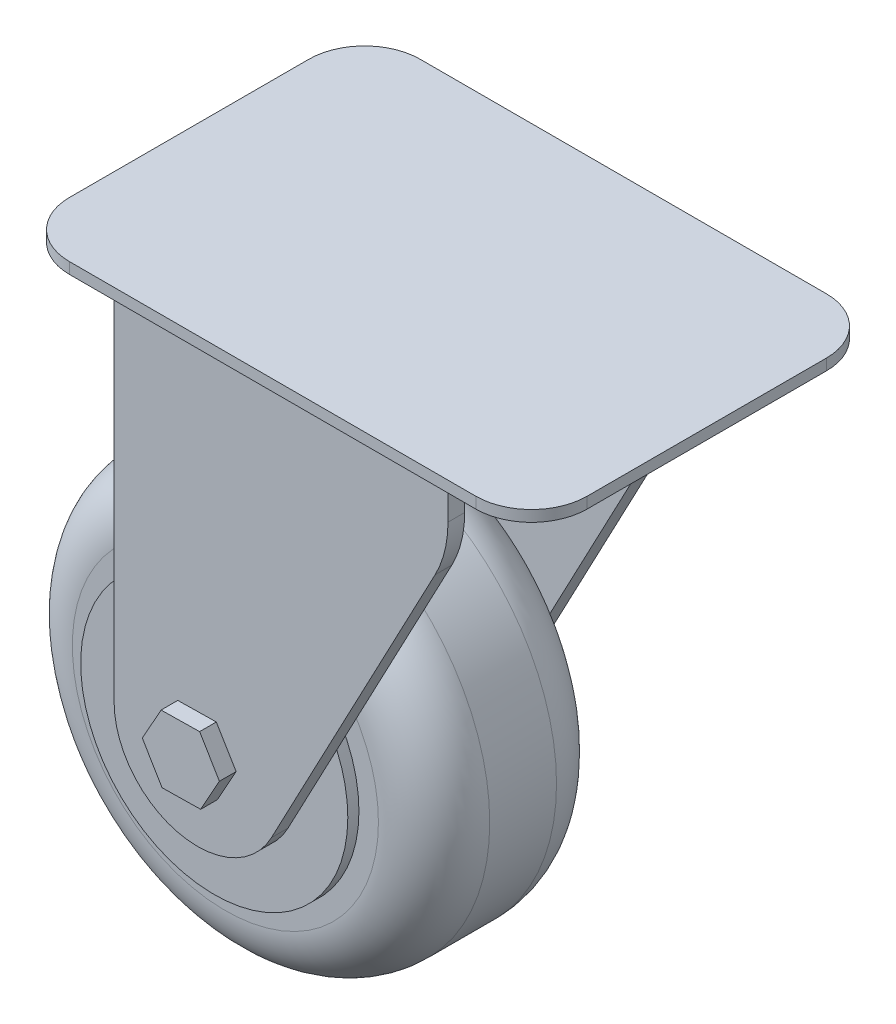
SolidWorks part; units mm, degrees
ref_plane "정면" through (0, 0, 0) normal (0, 0, 1) x (1, 0, 0)
ref_plane "윗면" through (0, 0, 0) normal (0, 1, 0) x (1, 0, 0)
ref_plane "우측면" through (0, 0, 0) normal (1, 0, 0) x (0, 0, -1)
sketch "스케치1" plane through (0, 0, 0) normal (0, 0, 1) x (1, 0, 0)
  line L0 (0, 0) -> (48.102, 0) construction
  line L1 (3.3687, 6.0541) -> (-3.5586, 5.9444)
  line L2 (-3.5586, 5.9444) -> (-6.9273, -0.1096)
  line L3 (-6.9273, -0.1096) -> (-3.3687, -6.0541)
  line L4 (-3.3687, -6.0541) -> (3.5586, -5.9444)
  line L5 (3.5586, -5.9444) -> (6.9273, 0.1096)
  line L6 (6.9273, 0.1096) -> (3.3687, 6.0541)
  circle A0 centre (0, 0) radius 37.5
  circle A1 centre (0, 0) radius 24
  circle A3 centre (0, 0) radius 6 construction
  dimension "D1" = 75
  dimension "D2" = 48
  dimension "D3" = 12
  dimension "D4" = 0.907
extrude "보스-돌출1" add sketch "스케치1" along normal blind 16 and the other way blind 16 contours A0 A1 region at (-36.4393, 0, 0)
extrude "보스-돌출2" add sketch "스케치1<3>" along normal blind 18 and the other way blind 18 contours A1 L6 L5 L4 L3 L2 L1 region at (-23.3212, 0, 0)
sketch "스케치1<3>" plane through (0, 0, 0) normal (0, 0, 1) x (1, 0, 0) same geometry as "스케치1"
extrude "보스-돌출3" add sketch "스케치1<4>" along normal blind 24 and the other way blind 24 contours L5 L6 L1 L2 L3 L4 region at (0, 0, 0)
sketch "스케치1<4>" plane through (0, 0, 0) normal (0, 0, 1) x (1, 0, 0) same geometry as "스케치1"
sketch "스케치2" plane through (0, 0, 18) normal (0, 0, 1) x (1, 0, 0)
  line L0 (-3.5586, 5.9444) -> (-6.9273, -0.1096)
  line L1 (-3.5586, 5.9444) -> (-6.9273, -0.1096)
  line L2 (3.3687, 6.0541) -> (-3.5586, 5.9444)
  line L3 (3.3687, 6.0541) -> (-3.5586, 5.9444)
  line L4 (-6.9273, -0.1096) -> (-3.3687, -6.0541)
  line L5 (-6.9273, -0.1096) -> (-3.3687, -6.0541)
  line L6 (-3.3687, -6.0541) -> (3.5586, -5.9444)
  line L7 (-3.3687, -6.0541) -> (3.5586, -5.9444)
  line L8 (3.5586, -5.9444) -> (6.9273, 0.1096)
  line L9 (3.5586, -5.9444) -> (6.9273, 0.1096)
  line L10 (6.9273, 0.1096) -> (3.3687, 6.0541)
  line L11 (6.9273, 0.1096) -> (3.3687, 6.0541)
  line L12 (0, 0) -> (63.2257, 0) construction
  line L13 (0, 0) -> (0, 87.7464) construction
  line L14 (-15, 0) -> (-15, 68)
  line L15 (-15, 68) -> (45, 68)
  line L16 (45, 68) -> (45, 57.9632)
  line L17 (42.6796, 48.6126) -> (13.2597, -7.0129)
  line L18 (0, 68) -> (0, 75)
  line L19 (0, 75) -> (45, 75)
  line L20 (45, 75) -> (45, 68)
  line L21 (0, 73) -> (45, 73)
  circle A0 centre (0, 0) radius 15
  arc A1 (45, 57.9632) -> (42.6796, 48.6126) centre (25, 57.9632) cw
  point P20 (45, 53)
  line M2 (3.3687, 6.0541) -> (6.9273, 0.1096)
  line M3 (6.9273, 0.1096) -> (3.5586, -5.9444)
  line M4 (3.5586, -5.9444) -> (-3.3687, -6.0541)
  line M5 (-3.3687, -6.0541) -> (-6.9273, -0.1096)
  line M6 (-6.9273, -0.1096) -> (-3.5586, 5.9444)
  line M7 (-3.5586, 5.9444) -> (3.3687, 6.0541)
  circle M8 centre (0, 0) radius 24
  dimension "D2" = 30
  dimension "D5" = 20
  dimension "D1" = 68
  dimension "D3" = 15
  dimension "D4" = 60
  dimension "D6" = 75
  dimension "D7" = 2
extrude "보스-돌출4" add sketch "스케치2" along normal blind 3 contours A1 L16 L15 L14 L17 M8 | A0 L17 L14 M8 | A0 M7 M2 M3 M4 M5 M6 region at (3.6956, 14.8921, 18) region at (0, 14.5757, 18) region at (12.8504, 45.3629, 18)
mirror "대칭 복사1" about plane through (0, 0, 0) normal (0, 0, 1) of "보스-돌출4"
sketch "스케치3" plane through (0, 0, 18) normal (0, 0, -1) x (-1, 0, 0)
  line L0 (-45, 65) -> (15, 65)
  line L4 (15, 18.735) -> (15, 68)
  line L5 (15, 68) -> (-45, 68)
  line L6 (-45, 68) -> (-45, 57.9632)
  line L7 (-42.6796, 48.6126) -> (-22.0188, 9.5484)
  line L8 (15, 18.735) -> (15, 68)
  line L9 (15, 68) -> (-45, 68)
  line L10 (-45, 68) -> (-45, 57.9632)
  line L11 (-42.6796, 48.6126) -> (-22.0188, 9.5484)
  arc A2 (15, 18.735) -> (-22.0188, 9.5484) centre (0, 0) ccw
  arc A3 (-45, 57.9632) -> (-42.6796, 48.6126) centre (-25, 57.9632) ccw
  arc A4 (15, 18.735) -> (-22.0188, 9.5484) centre (0, 0) ccw
  arc A5 (-45, 57.9632) -> (-42.6796, 48.6126) centre (-25, 57.9632) ccw
  point P10 (-15, 68)
  line M9 (15, 18.735) -> (15, 68)
  line M10 (15, 68) -> (-45, 68)
  line M11 (-45, 68) -> (-45, 57.9632)
  dimension "D2" = 3
  dimension "D1" = 0
extrude "보스-돌출5" add sketch "스케치3" along normal up to body separate body contours L0 M11 M9 M10 region at (15, 66.5, 18)
sketch "스케치4" plane through (0, 68, 0) normal (0, 1, 0) x (1, 0, 0)
  line L0 (0, 0) -> (62.5585, 0) construction
  line L4 (45, -21) -> (45, 21)
  line L5 (45, 21) -> (-15, 21)
  line L6 (-15, 21) -> (-15, -21)
  line L7 (-15, -21) -> (45, -21)
  line L8 (45, -21) -> (45, 21)
  line L9 (45, 21) -> (-15, 21)
  line L10 (-15, 21) -> (-15, -21)
  line L11 (-15, -21) -> (45, -21)
  circle A0 centre (24, 0) radius 21
  dimension "D1" = 0
extrude "보스-돌출6" add sketch "스케치4" along normal blind 5 contours L0 A0 | A0 L0 region at (24, 68, -8.9127) region at (24, 68, 8.9127)
sketch "스케치5" plane through (0, 73, 0) normal (0, 1, 0) x (1, 0, 0)
  line L1 (-22.5, -31.5) -> (70.5, -31.5)
  line L2 (-22.5, -31.5) -> (-22.5, 31.5)
  line L3 (-22.5, 31.5) -> (70.5, 31.5)
  line L4 (70.5, -31.5) -> (70.5, 31.5)
  line L5 (-22.5, -31.5) -> (70.5, 31.5) construction
  line L6 (-22.5, 31.5) -> (70.5, -31.5) construction
  circle A1 centre (24, 0) radius 21
  circle A2 centre (24, 0) radius 21
  circle M1 centre (24, 0) radius 21
  dimension "D2" = 63
  dimension "D3" = 93
  dimension "D1" = 0
extrude "보스-돌출7" add sketch "스케치5" along direction (0, 1, 0) on the side of the normal blind 2 contours M1 region at (24, 73, 0)
extrude "보스-돌출8" add sketch "스케치5<3>" along normal blind 2
sketch "스케치5<3>" plane through (0, 73, 0) normal (0, 1, 0) x (1, 0, 0) same geometry as "스케치5"
fillet "필렛1" radius 10 4 edges at (-22.5, 74, 31.5) (-22.5, 74, -31.5) (70.5, 74, -31.5) (70.5, 74, 31.5)
fillet "필렛2" radius 10 1 edges at (37.5, 0, 16)
fillet "필렛3" radius 10 1 edges at (37.5, 0, -16)
